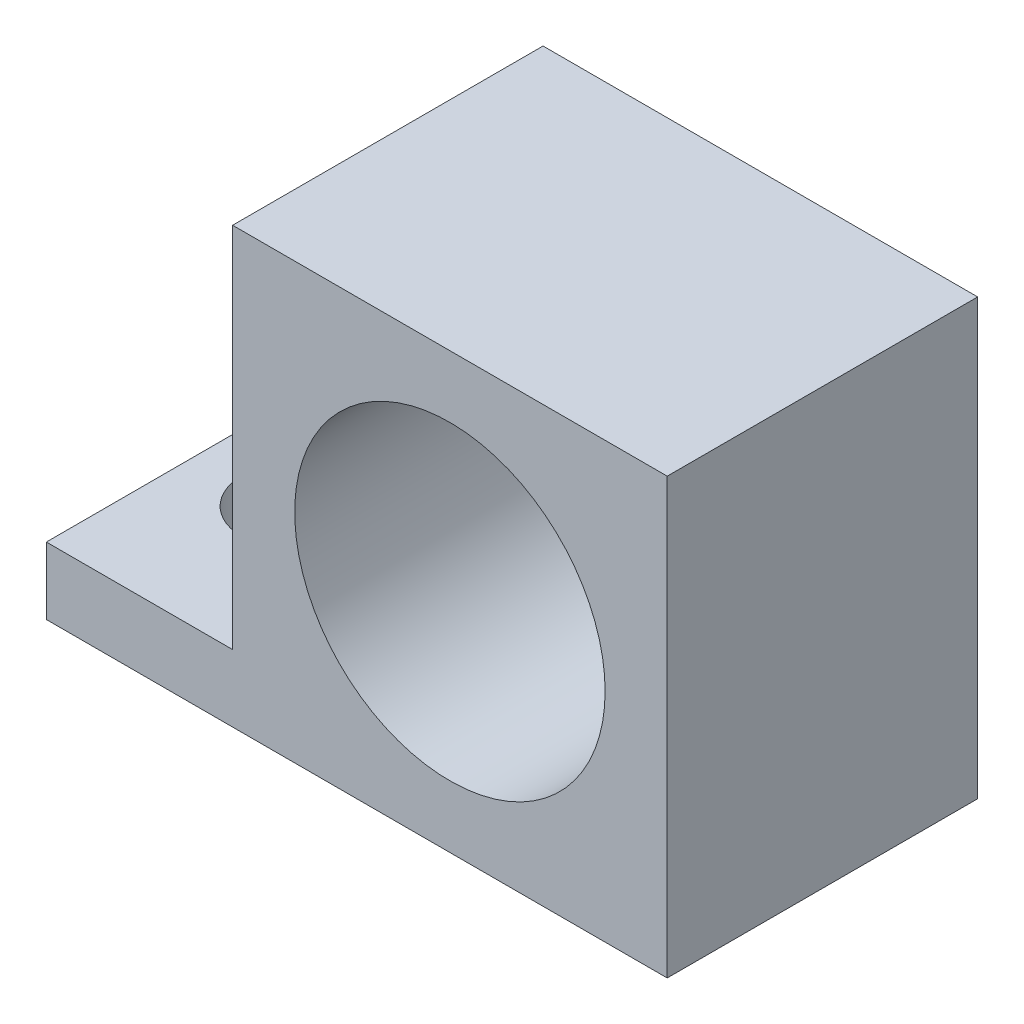
SolidWorks part; units mm, degrees
material "6061 Alloy"
ref_plane "Front Plane" through (0, 0, 0) normal (0, 0, 1) x (1, 0, 0)
ref_plane "Top Plane" through (0, 0, 0) normal (0, 1, 0) x (1, 0, 0)
ref_plane "Right Plane" through (0, 0, 0) normal (1, 0, 0) x (0, 0, -1)
sketch "Sketch1" plane through (0, 0, 0) normal (0, 0, 1) x (1, 0, 0)
  line L0 (0, 0) -> (20, 0)
  line L1 (20, 0) -> (20, 14)
  line L2 (20, 14) -> (6, 14)
  line L3 (6, 14) -> (6, 2.1623)
  line L4 (6, 2.1623) -> (0, 2.1623)
  line L5 (0, 2.1623) -> (0, 0)
  circle A0 centre (13, 7) radius 5
  point P9 (20, 7)
  point P10 (13, 14)
  dimension "D1" = 10
  dimension "D2" = 14
  dimension "D3" = 6
extrude "Boss-Extrude1" add sketch "Sketch1" along normal blind 10
hole_wizard "M3 Clearance Hole1" positions "Sketch3" profile "Sketch4" hole size "M3" standard "ISO" end condition through all
sketch "Sketch3" plane through (0, 2.1623, 0) normal (0, 1, 0) x (-1, 0, 0)
  line L0 (-6, 10) -> (0, 10) construction
  line L1 (0, 10) -> (0, 0) construction
  point P0 (-3, 5)
  point P5 (-3, 10)
  point P8 (0, 5)
sketch "Sketch4" plane through (3, 2.1623, 5) normal (1, 0, 0) x (0, 0, 1)
  line L0 (0, 0) -> (0, 2.1623)
  line L1 (0, 2.1623) -> (1.7, 2.1623)
  line L2 (1.7, 2.1623) -> (1.7, 0)
  line L5 (1.7, 0) -> (0, 0)
  line L11 (0, -6.35) -> (0, 107.95) construction
  dimension "Thru Hole Dia." = 3.4
  dimension "Thru Hole Depth" = 2.1623
